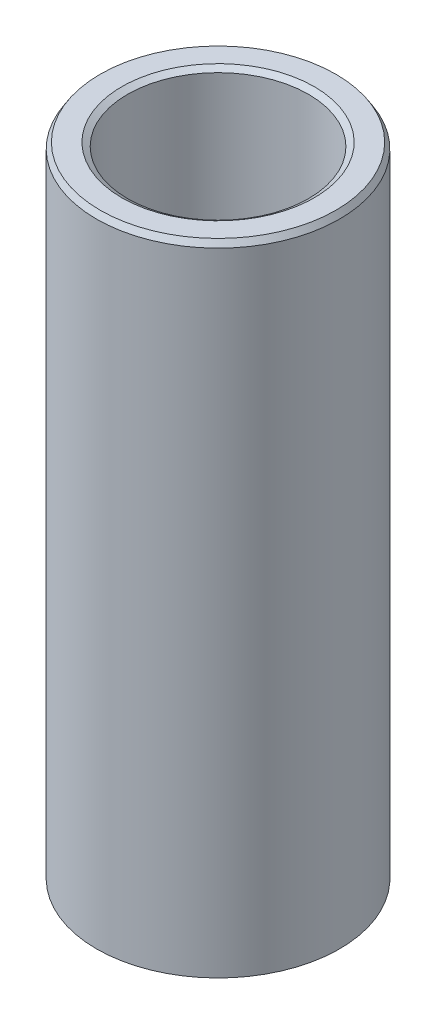
SolidWorks part; units mm, degrees
ref_plane "Front Plane" through (0, 0, 0) normal (0, 0, 1) x (1, 0, 0)
ref_plane "Top Plane" through (0, 0, 0) normal (0, 1, 0) x (1, 0, 0)
ref_plane "Right Plane" through (0, 0, 0) normal (1, 0, 0) x (0, 0, -1)
sketch "Sketch1" plane through (0, 0, 0) normal (0, 1, 0) x (1, 0, 0)
  circle A0 centre (0, 0) radius 22.5
  dimension "SLEEVE_OD" = 45
extrude "Boss-Extrude1" add sketch "Sketch1" along normal blind 118.7899
sketch "Sketch2" plane through (0, 0, 0) normal (0, 1, 0) x (1, 0, 0)
  circle A0 centre (0, 0) radius 16.7451
  dimension "BORE_D" = 33.4902
extrude "Cut-Extrude1" cut sketch "Sketch2" along normal through all
chamfer "Chamfer1" distance 1.0802 angle 32.151 4 edges at (0, 118.7899, 16.7451) (0, 0, 16.7451) (0, 0, 22.5) (0, 118.7899, 22.5) first distance on face at (0, 118.7899, 16.7451) first distance on face at (0, 0, 16.7451) first distance on face at (0, 118.7899, 22.5)
